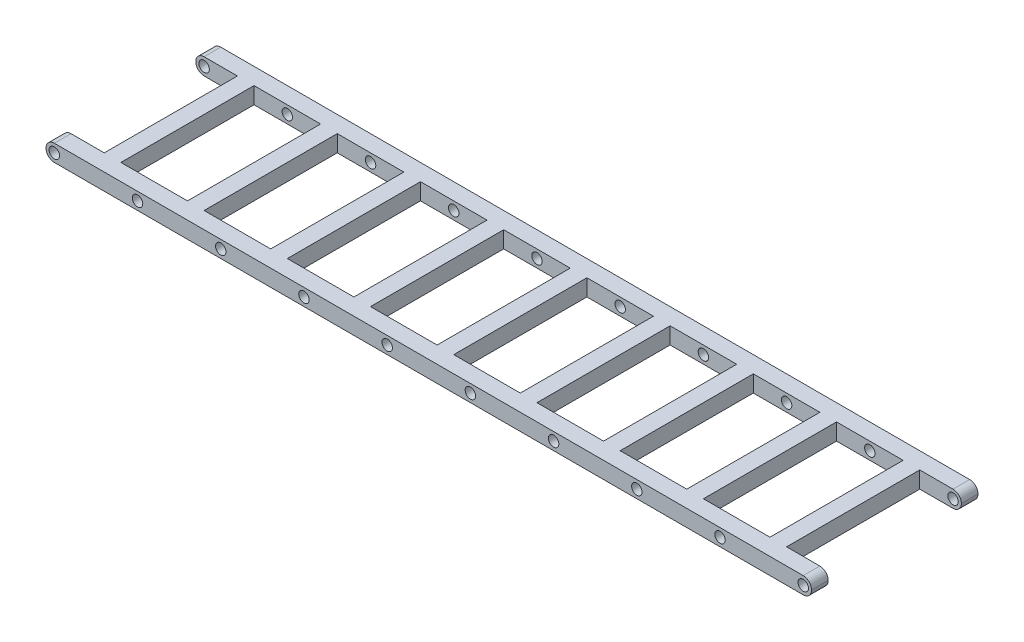
SolidWorks part; units mm, degrees
ref_plane "Front Plane" through (0, 0, 0) normal (0, 0, 1) x (1, 0, 0)
ref_plane "Top Plane" through (0, 0, 0) normal (0, 1, 0) x (1, 0, 0)
ref_plane "Right Plane" through (0, 0, 0) normal (1, 0, 0) x (0, 0, -1)
sketch "Sketch1" plane through (0, 0, 0) normal (0, 1, 0) x (1, 0, 0)
  line L0 (-146.05, 25.4) -> (-130.175, 25.4)
  line L1 (-146.05, 31.75) -> (146.05, 31.75)
  line L2 (-146.05, 31.75) -> (-146.05, 25.4)
  line L3 (-146.05, -31.75) -> (146.05, -31.75)
  line L4 (146.05, 31.75) -> (146.05, 25.4)
  line L5 (-146.05, 31.75) -> (146.05, -31.75) construction
  line L6 (-146.05, -31.75) -> (146.05, 31.75) construction
  line L8 (-146.05, -25.4) -> (-130.175, -25.4)
  line L10 (0, 31.75) -> (0, -31.75) construction
  line L11 (-3.175, 25.4) -> (-3.175, -25.4)
  line L12 (130.175, 25.4) -> (130.175, -25.4)
  line L13 (123.825, 25.4) -> (123.825, -25.4)
  line L14 (-3.175, 31.75) -> (-3.175, -31.75) construction
  line L15 (-28.575, 25.4) -> (-28.575, -25.4)
  line L16 (-34.925, 25.4) -> (-34.925, -25.4)
  line L17 (-60.325, 25.4) -> (-60.325, -25.4)
  line L18 (-66.675, 25.4) -> (-66.675, -25.4)
  line L19 (-92.075, 25.4) -> (-92.075, -25.4)
  line L20 (-98.425, 25.4) -> (-98.425, -25.4)
  line L21 (-123.825, 25.4) -> (-123.825, -25.4)
  line L22 (-130.175, 25.4) -> (-130.175, -25.4)
  line L23 (-146.05, -25.4) -> (-146.05, -31.75)
  line L24 (146.05, -25.4) -> (146.05, -31.75)
  line L25 (98.425, 25.4) -> (98.425, -25.4)
  line L26 (92.075, 25.4) -> (92.075, -25.4)
  line L27 (66.675, 25.4) -> (66.675, -25.4)
  line L28 (60.325, 25.4) -> (60.325, -25.4)
  line L29 (34.925, 25.4) -> (34.925, -25.4)
  line L30 (28.575, 25.4) -> (28.575, -25.4)
  line L31 (3.175, 25.4) -> (3.175, -25.4)
  line L32 (-123.825, 25.4) -> (-98.425, 25.4)
  line L33 (-123.825, -25.4) -> (-98.425, -25.4)
  line L34 (-92.075, 25.4) -> (-66.675, 25.4)
  line L35 (-92.075, -25.4) -> (-66.675, -25.4)
  line L36 (-28.575, -25.4) -> (-3.175, -25.4)
  line L37 (-60.325, 25.4) -> (-34.925, 25.4)
  line L38 (-28.575, 25.4) -> (-3.175, 25.4)
  line L39 (3.175, 25.4) -> (28.575, 25.4)
  line L40 (3.175, -25.4) -> (28.575, -25.4)
  line L41 (34.925, -25.4) -> (60.325, -25.4)
  line L42 (34.925, 25.4) -> (60.325, 25.4)
  line L43 (66.675, 25.4) -> (92.075, 25.4)
  line L44 (66.675, -25.4) -> (92.075, -25.4)
  line L45 (98.425, 25.4) -> (123.825, 25.4)
  line L46 (98.425, -25.4) -> (123.825, -25.4)
  line L47 (130.175, -25.4) -> (146.05, -25.4)
  line L48 (130.175, 25.4) -> (146.05, 25.4)
  line L49 (-60.325, -25.4) -> (-34.925, -25.4)
  point P0 (0, 0)
  dimension "D1" = 63.5
  dimension "D2" = 292.1
  dimension "D4" = 3.175
  dimension "D3" = 6.35
  dimension "D14" = 6.35
  dimension "D6" = 25.4
  dimension "D7" = 6.35
  dimension "D8" = 25.4
  dimension "D9" = 6.35
  dimension "D10" = 25.4
  dimension "D11" = 6.35
  dimension "D12" = 25.4
  dimension "D13" = 6.35
extrude "Boss-Extrude1" add sketch "Sketch1" against normal blind 6.35
sketch "Sketch2" plane through (0, 0, 31.75) normal (0, 0, 1) x (1, 0, 0)
  line L0 (-142.875, 0) -> (-142.875, -6.35) construction
  line L1 (0, 0) -> (0, -6.35) construction
  line L2 (-123.825, 0) -> (-98.425, 0) construction
  line L3 (-123.825, 0) -> (-98.425, 0)
  line L4 (146.05, 0) -> (-146.05, 0)
  line L5 (-146.05, 0) -> (-146.05, -6.35)
  line L6 (-146.05, -6.35) -> (146.05, -6.35)
  line L7 (146.05, -6.35) -> (146.05, 0)
  line L8 (146.05, 0) -> (-146.05, 0)
  line L9 (-146.05, 0) -> (-146.05, -6.35)
  line L10 (-146.05, -6.35) -> (146.05, -6.35)
  line L11 (146.05, -6.35) -> (146.05, 0)
  circle A0 centre (-142.875, -3.175) radius 3.81
  circle A1 centre (-111.125, -3.175) radius 3.81
  circle A2 centre (-15.875, -3.175) radius 3.81
  circle A3 centre (-79.375, -3.175) radius 3.81
  circle A4 centre (-47.625, -3.175) radius 3.81
  circle A5 centre (-142.875, -3.175) radius 1.9939
  circle A6 centre (-111.125, -3.175) radius 1.9939
  circle A7 centre (-79.375, -3.175) radius 1.9939
  circle A8 centre (-47.625, -3.175) radius 1.9939
  circle A9 centre (-15.875, -3.175) radius 1.9939
  circle A10 centre (15.875, -3.175) radius 1.9939
  circle A11 centre (47.625, -3.175) radius 1.9939
  circle A12 centre (79.375, -3.175) radius 1.9939
  circle A13 centre (111.125, -3.175) radius 1.9939
  circle A14 centre (142.875, -3.175) radius 1.9939
  point P4 (-146.05, -3.175)
  point P15 (-111.125, 0)
  dimension "D1" = 7.62
  dimension "D4" = 7.62
  dimension "D5" = 7.62
  dimension "D6" = 7.62
  dimension "D7" = 7.62
  dimension "D11" = 3.9878
  dimension "D12" = 3.9878
  dimension "D13" = 3.9878
  dimension "D14" = 3.9878
  dimension "D15" = 3.9878
  dimension "D8" = 31.75
  dimension "D9" = 31.75
  dimension "D10" = 31.75
  dimension "D2" = 0
  dimension "D3" = 3.175
extrude "Cut-Extrude1" cut sketch "Sketch2" against normal up to surface (63.5 mm away) contours A5 | A6 | A7 | A8 | A9 | A10 | A11 | A12 | A13 | A14 region at (-142.875, -3.175, 31.75) region at (-111.125, -3.175, 31.75) region at (-79.375, -3.175, 31.75) region at (-47.625, -3.175, 31.75) region at (-15.875, -3.175, 31.75) region at (15.875, -3.175, 31.75) region at (47.625, -3.175, 31.75) region at (79.375, -3.175, 31.75) region at (111.125, -3.175, 31.75) region at (142.875, -3.175, 31.75) up to face at (0, -3.175, -31.75)
fillet "Fillet2" radius 3.175 8 edges at (-146.05, -6.35, 28.575) (-146.05, 0, 28.575) (-146.05, -6.35, -28.575) (-146.05, 0, -28.575) (146.05, -6.35, -28.575) (146.05, 0, -28.575) (146.05, -6.35, 28.575) (146.05, 0, 28.575)
